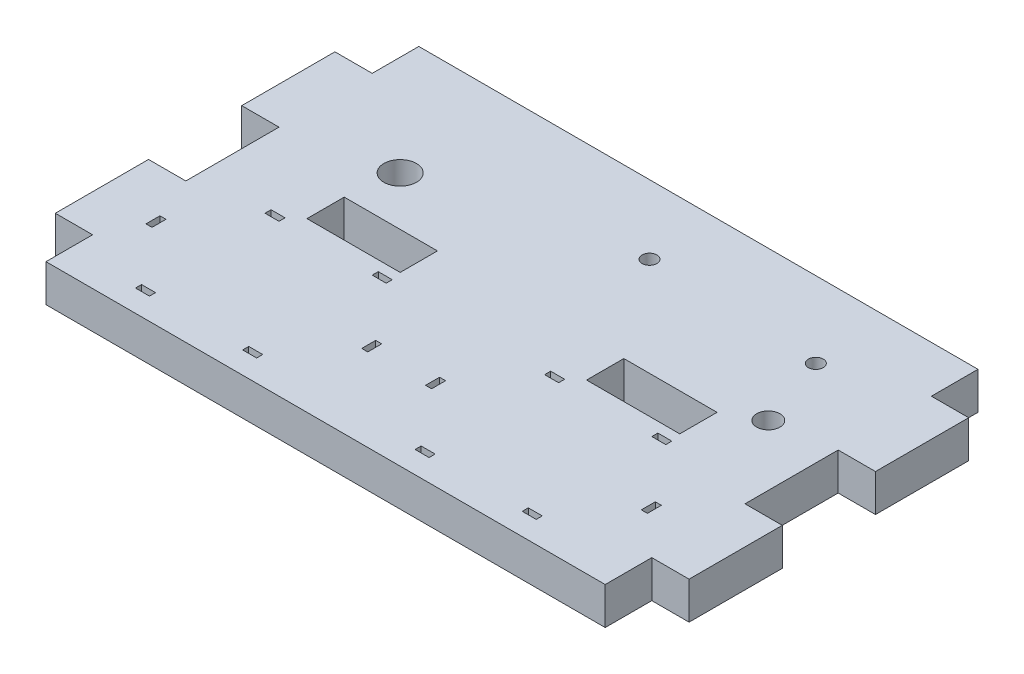
SolidWorks part; units mm, degrees
ref_plane "Front Plane" through (0, 0, 0) normal (0, 0, 1) x (1, 0, 0)
ref_plane "Top Plane" through (0, 0, 0) normal (0, 1, 0) x (1, 0, 0)
ref_plane "Right Plane" through (0, 0, 0) normal (1, 0, 0) x (0, 0, -1)
sketch "Sketch1" plane through (0, 0, 0) normal (0, 1, 0) x (1, 0, 0)
  line L0 (-66.0627, 0) -> (65.2437, 0) construction
  line L1 (-60, 40) -> (60, 40)
  line L2 (-60, 40) -> (-60, -40)
  line L3 (-60, -40) -> (60, -40)
  line L4 (60, 40) -> (60, -40)
  line L5 (27.5, -7.5) -> (27.5, -34) construction
  line L6 (45, 10) -> (-18.5, 10) construction
  line L7 (45, 10) -> (45, 35) construction
  line L8 (45, 35) -> (-18.5, 35) construction
  line L9 (-18.5, 10) -> (-18.5, 35) construction
  line L10 (5, -7.5) -> (50, -7.5) construction
  line L11 (5, -7.5) -> (5, -34) construction
  line L12 (5, -34) -> (50, -34) construction
  line L13 (50, -7.5) -> (50, -34) construction
  line L14 (5, -20.75) -> (50, -20.75) construction
  line L15 (40.5, -7.5) -> (37.5, -7.5)
  line L16 (14.5, -7.5) -> (17.5, -7.5)
  line L17 (14.5, -7.5) -> (14.5, -6.2)
  line L18 (14.5, -6.2) -> (17.5, -6.2)
  line L19 (17.5, -7.5) -> (17.5, -6.2)
  line L20 (5, -19.25) -> (3.7, -19.25)
  line L21 (5, -19.25) -> (5, -22.25)
  line L22 (5, -22.25) -> (3.7, -22.25)
  line L23 (3.7, -19.25) -> (3.7, -22.25)
  line L24 (37.5, -7.5) -> (37.5, -6.2)
  line L25 (40.5, -6.2) -> (37.5, -6.2)
  line L26 (40.5, -7.5) -> (40.5, -6.2)
  line L27 (50, -19.25) -> (51.3, -19.25)
  line L28 (51.3, -19.25) -> (51.3, -22.25)
  line L29 (50, -22.25) -> (51.3, -22.25)
  line L30 (50, -19.25) -> (50, -22.25)
  line L31 (37.5, -34) -> (37.5, -35.3)
  line L32 (40.5, -34) -> (37.5, -34)
  line L33 (40.5, -34) -> (40.5, -35.3)
  line L34 (40.5, -35.3) -> (37.5, -35.3)
  line L35 (14.5, -34) -> (17.5, -34)
  line L36 (17.5, -34) -> (17.5, -35.3)
  line L37 (14.5, -34) -> (14.5, -35.3)
  line L38 (14.5, -35.3) -> (17.5, -35.3)
  line L39 (-2.5, -65.1553) -> (-2.5, 67.8606) construction
  line L41 (-42, 14.5) -> (-60, 14.5) construction
  line L43 (-40, 4) -> (-24.847, 4) construction
  line L44 (-38.5, 11) -> (-38.5, 4) construction
  line L45 (68, 4) -> (40, 4) construction
  line L46 (-19.5, -35.3) -> (-22.5, -35.3)
  line L47 (-19.5, -34) -> (-19.5, -35.3)
  line L48 (-22.5, -34) -> (-22.5, -35.3)
  line L49 (-19.5, -34) -> (-22.5, -34)
  line L50 (-45.5, -35.3) -> (-42.5, -35.3)
  line L51 (-45.5, -34) -> (-45.5, -35.3)
  line L52 (-45.5, -34) -> (-42.5, -34)
  line L53 (-42.5, -34) -> (-42.5, -35.3)
  line L54 (-55, -19.25) -> (-55, -22.25)
  line L55 (-55, -22.25) -> (-56.3, -22.25)
  line L56 (-56.3, -19.25) -> (-56.3, -22.25)
  line L57 (-55, -19.25) -> (-56.3, -19.25)
  line L58 (-45.5, -7.5) -> (-45.5, -6.2)
  line L59 (-45.5, -6.2) -> (-42.5, -6.2)
  line L60 (-42.5, -7.5) -> (-42.5, -6.2)
  line L61 (-8.7, -19.25) -> (-8.7, -22.25)
  line L62 (-10, -22.25) -> (-8.7, -22.25)
  line L63 (-10, -19.25) -> (-10, -22.25)
  line L64 (-10, -19.25) -> (-8.7, -19.25)
  line L65 (-22.5, -7.5) -> (-22.5, -6.2)
  line L66 (-19.5, -6.2) -> (-22.5, -6.2)
  line L67 (-19.5, -7.5) -> (-19.5, -6.2)
  line L68 (-19.5, -7.5) -> (-22.5, -7.5)
  line L69 (-45.5, -7.5) -> (-42.5, -7.5)
  circle A0 centre (41.5, 23.7) radius 1.6
  circle A1 centre (4.3, 25.2) radius 1.6
  circle A2 centre (-38.5, 14.5) radius 3.5
  circle A3 centre (47, 8) radius 2.5
  point P4 (60, 0)
  point P6 (0, 40)
  point P33 (5, -20.75)
  point P87 (0, 0)
  dimension "D5" = 3.2
  dimension "D10" = 3.2
  dimension "D17" = 3
  dimension "D18" = 1.3
  dimension "D23" = 18
  dimension "D24" = 13
  dimension "D26" = 7
  dimension "D1" = 120
  dimension "D2" = 80
  dimension "D3" = 10
  dimension "D4" = 15
  dimension "D6" = 3.5
  dimension "D7" = 13.7
  dimension "D8" = 63.5
  dimension "D9" = 25
  dimension "D11" = 40.7
  dimension "D12" = 15.2
  dimension "D13" = 26.5
  dimension "D14" = 45
  dimension "D15" = 7.5
  dimension "D16" = 15
  dimension "D19" = 3
  dimension "D20" = 1.3
  dimension "D21" = 20
  dimension "D22" = 10
  dimension "D25" = 4
extrude "Boss-Extrude1" add sketch "Sketch1" along normal blind 8
sketch "Sketch2" plane through (0, 0, 0) normal (0, -1, 0) x (-1, 0, 0)
  line L1 (-7.4754, 25.2) -> (-5.8877, 22.45)
  line L2 (-5.8877, 22.45) -> (-2.7123, 22.45)
  line L3 (-2.7123, 22.45) -> (-1.1246, 25.2)
  line L4 (-1.1246, 25.2) -> (-2.7123, 27.95)
  line L5 (-2.7123, 27.95) -> (-5.8877, 27.95)
  line L6 (-5.8877, 27.95) -> (-7.4754, 25.2)
  line L7 (-44.6754, 23.7) -> (-43.0877, 20.95)
  line L8 (-43.0877, 20.95) -> (-39.9123, 20.95)
  line L9 (-39.9123, 20.95) -> (-38.3246, 23.7)
  line L10 (-38.3246, 23.7) -> (-39.9123, 26.45)
  line L11 (-39.9123, 26.45) -> (-43.0877, 26.45)
  line L12 (-43.0877, 26.45) -> (-44.6754, 23.7)
  circle A0 centre (-4.3, 25.2) radius 2.75 construction
  circle A1 centre (-41.5, 23.7) radius 2.75 construction
  dimension "D1" = 5.5
  dimension "D2" = 5.5
extrude "Cut-Extrude1" cut sketch "Sketch2" against normal blind 4
sketch "Sketch3" plane through (-60, 0, 0) normal (-1, 0, 0) x (0, 0, 1)
  line L0 (-40, 8) -> (-40, 0) construction
  line L1 (-30, 0) -> (-10, 0)
  line L2 (-30, 0) -> (-30, 8)
  line L3 (-30, 8) -> (-10, 8)
  line L4 (-10, 0) -> (-10, 8)
  line L5 (-40, 0) -> (40, 0) construction
  line L6 (0, 15.2289) -> (0, -7.9114) construction
  line L7 (10, 0) -> (10, 8)
  line L8 (30, 8) -> (10, 8)
  line L9 (30, 0) -> (30, 8)
  line L10 (30, 0) -> (10, 0)
  dimension "D1" = 20
  dimension "D2" = 20
extrude "Boss-Extrude2" add sketch "Sketch3" along normal blind 8
ref_plane "Plane1" through (0, 0, 0) normal (-1, 0, 0) x (0, 0, 1)
mirror "Mirror1" about plane through (0, 0, 0) normal (-1, 0, 0) of "Boss-Extrude2"
sketch "Sketch5" plane through (0, 0, 0) normal (0, -1, 0) x (-1, 0, 0)
  line L0 (74.0532, 0) -> (-79.4319, 0) construction
  line L1 (20, 4) -> (40, 4)
  line L2 (20, 4) -> (20, -4)
  line L3 (20, -4) -> (40, -4)
  line L4 (40, 4) -> (40, -4)
  line L5 (0, -4.4) -> (0, 4.4) construction
  point P7 (20, 0)
  dimension "D1" = 20
  dimension "D2" = 8
  dimension "D3" = 20
extrude "Cut-Extrude3" cut sketch "Sketch5" against normal up to next
mirror "Mirror2" about plane through (0, 0, 0) normal (-1, 0, 0) of "Cut-Extrude3"
